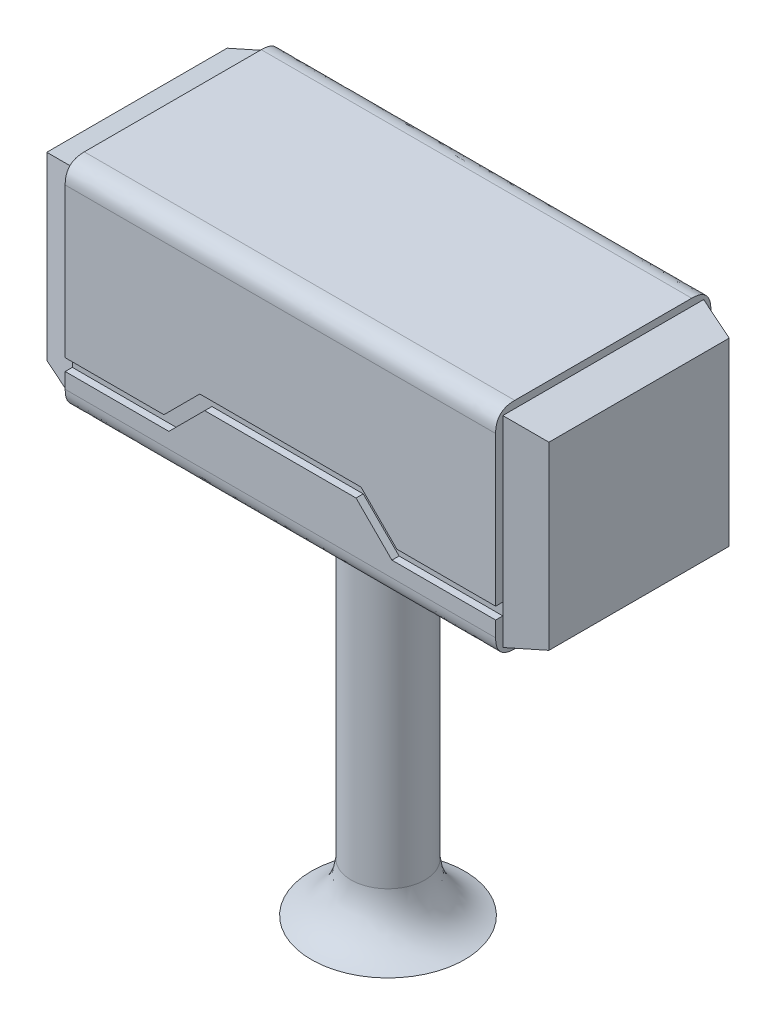
SolidWorks part; units mm, degrees
ref_plane "前视基准面" through (0, 0, 0) normal (0, 0, 1) x (1, 0, 0)
ref_plane "上视基准面" through (0, 0, 0) normal (0, 1, 0) x (1, 0, 0)
ref_plane "右视基准面" through (0, 0, 0) normal (1, 0, 0) x (0, 0, -1)
sketch "草图1" plane through (0, 0, 0) normal (0, 0, 1) x (1, 0, 0)
  line L1 (-90, 45) -> (90, 45)
  line L2 (-90, 45) -> (-90, -45)
  line L3 (-90, -45) -> (90, -45)
  line L4 (90, 45) -> (90, -45)
  line L5 (-90, 45) -> (90, -45) construction
  line L6 (-90, -45) -> (90, 45) construction
  point P0 (0, 0)
  point P5 (0, 0)
extrude "凸台-拉伸1" add sketch "草图1" along normal mid plane 90
sketch "草图3" plane through (90, 0, 0) normal (1, 0, 0) x (0, 0, -1)
  line L8 (42, -42) -> (42, 42)
  line L9 (42, 42) -> (-42, 42)
  line L10 (-42, 42) -> (-42, -42)
  line L11 (-42, -42) -> (42, -42)
  line L12 (42, -42) -> (42, 42)
  line L13 (42, 42) -> (-42, 42)
  line L14 (-42, 42) -> (-42, -42)
  line L15 (-42, -42) -> (42, -42)
  dimension "D1" = 3
extrude "凸台-拉伸3" add sketch "草图3" along normal blind 15 draft 16 contours L12 L13 L14 L15
mirror "镜向2" about plane through (0, 0, 0) normal (1, 0, 0) of "凸台-拉伸3"
sketch "草图5" plane through (0, 0, -45) normal (0, 0, -1) x (-1, 0, 0)
  line L0 (-90, -25.551) -> (-48.71, -25.551)
  line L1 (-90, -42) -> (-90, 42) construction
  line L2 (-48.71, -25.551) -> (-33.7071, -10.5481)
  line L3 (-33.7071, -10.5481) -> (33.7071, -10.5481)
  line L4 (0, 35.9889) -> (0, -10.5481) construction
  line L5 (-90, -30.551) -> (-46.6389, -30.551)
  line L6 (-46.6389, -30.551) -> (-31.636, -15.5481)
  line L7 (-31.636, -15.5481) -> (31.636, -15.5481)
  line L8 (-33.7071, -10.5481) -> (-13.4822, -10.5481) construction
  line L9 (-31.636, -15.5481) -> (-13.4822, -15.5481) construction
  line L10 (46.6389, -30.551) -> (31.636, -15.5481)
  line L11 (90, -30.551) -> (46.6389, -30.551)
  line L12 (48.71, -25.551) -> (33.7071, -10.5481)
  line L13 (90, -25.551) -> (48.71, -25.551)
  line L14 (-90, -30.551) -> (-90, -25.551)
  line L15 (90, -30.551) -> (90, -25.551)
  point P24 (0, -15.5481)
  dimension "D1" = 5
extrude "切除-拉伸1" cut sketch "草图5" against normal blind 3
mirror "镜向3" about plane through (0, 0, 0) normal (0, 0, 1) of "切除-拉伸1"
fillet "圆角1" radius 8 4 edges at (0, -45, -45) (0, 45, -45) (0, 45, 45) (0, -45, 45) conic rho 0.5
ref_plane "基准面4" through (90, -45, 37) normal (-1, 0, 0) x (0, 0, 1)
ref_plane "基准面5" through (-90, -45, 37) normal (-1, 0, 0) x (0, 0, 1)
sketch "草图16" plane through (0, 0, 0) normal (0, 0, 1) x (1, 0, 0)
  line L0 (0, -45) -> (0, -205.0262)
  line L1 (90, -45) -> (-90, -45) construction
  line L2 (0, -45) -> (15.4347, -45)
  line L3 (15.4347, -45) -> (15.4347, -184.5053)
  line L4 (0, -205.0262) -> (32.0693, -205.0262)
  spline S0 degree 2 poles (15.4347, -184.5053) (16.9763, -200.4318) (32.0693, -205.0262) knots 0 0 0 1 1 1
revolve "旋转1" add sketch "草图16" angle 360 about L0
